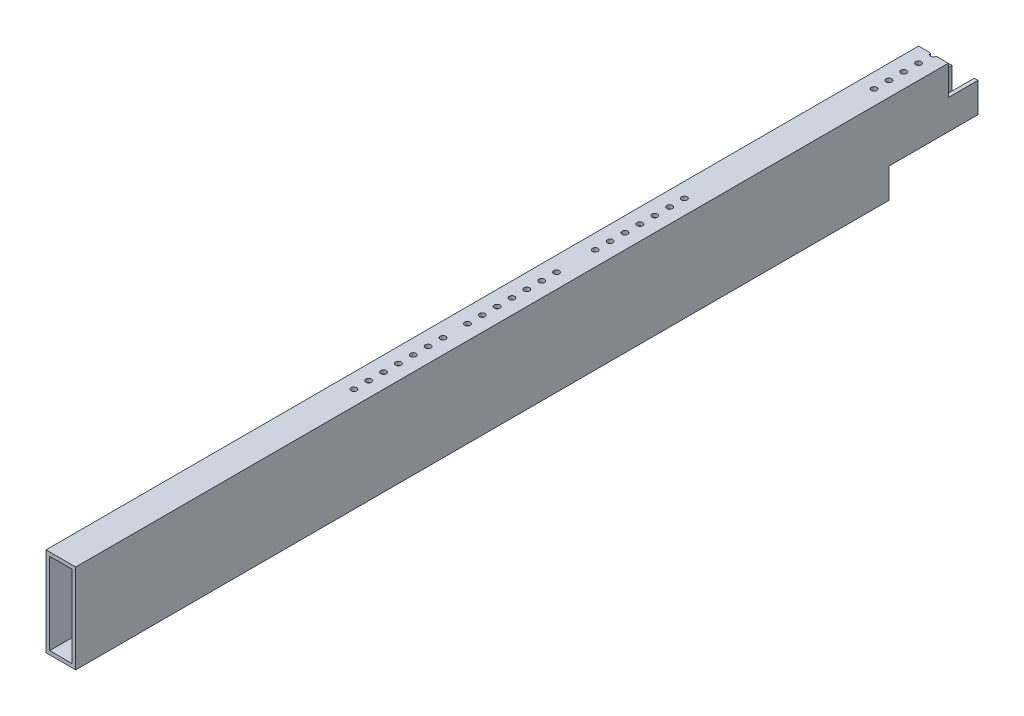
SolidWorks part; units mm, degrees
ref_plane "Front Plane" through (0, 0, 0) normal (0, 0, 1) x (1, 0, 0)
ref_plane "Top Plane" through (0, 0, 0) normal (0, 1, 0) x (1, 0, 0)
ref_plane "Right Plane" through (0, 0, 0) normal (1, 0, 0) x (0, 0, -1)
sketch "Sketch1" plane through (0, 0, 0) normal (0, 0, 1) x (1, 0, 0)
  line L1 (-12.7, -38.1) -> (12.7, -38.1)
  line L2 (-12.7, -38.1) -> (-12.7, 38.1)
  line L3 (-12.7, 38.1) -> (12.7, 38.1)
  line L4 (12.7, -38.1) -> (12.7, 38.1)
  line L5 (-12.7, -38.1) -> (12.7, 38.1) construction
  line L6 (-12.7, 38.1) -> (12.7, -38.1) construction
  point P0 (0, 0)
  dimension "D1" = 25.4
  dimension "D2" = 76.2
extrude "Boss-Extrude1" add sketch "Sketch1" along normal mid plane 771.398
shell "Shell1" thickness 3.175 removed face at (0, 0, -385.699) removed face at (0, 0, 385.699)
sketch "Sketch2" plane through (12.7, 0, 0) normal (1, 0, 0) x (0, 0, -1)
  line L1 (385.699, -38.1) -> (309.499, -38.1)
  line L2 (385.699, -38.1) -> (385.699, -12.7)
  line L3 (385.699, -12.7) -> (309.499, -12.7)
  line L4 (309.499, -38.1) -> (309.499, -12.7)
  dimension "D1" = 25.4
  dimension "D2" = 76.2
extrude "Cut-Extrude1" cut sketch "Sketch2" against normal through all
sketch "Sketch3" plane through (12.7, 0, 0) normal (1, 0, 0) x (0, 0, -1)
  line L1 (385.699, 38.1) -> (360.299, 38.1)
  line L2 (385.699, 38.1) -> (385.699, 12.7)
  line L3 (385.699, 12.7) -> (360.299, 12.7)
  line L4 (360.299, 38.1) -> (360.299, 12.7)
  dimension "D1" = 25.4
extrude "Cut-Extrude2" cut sketch "Sketch3" against normal through all
sketch "Sketch4" plane through (0, 38.1, 0) normal (0, 1, 0) x (1, 0, 0)
  line L0 (-12.7, 360.299) -> (12.7, 360.299) construction
  circle A0 centre (0, 147.3945) radius 2.3812
  circle A1 centre (0, 134.6945) radius 2.3812
  circle A2 centre (0, 121.9945) radius 2.3812
  circle A3 centre (0, 109.2945) radius 2.3812
  circle A4 centre (0, 96.5945) radius 2.3812
  circle A5 centre (0, 83.8945) radius 2.3812
  circle A6 centre (0, 71.1945) radius 2.3812
  circle A7 centre (0, 38.0987) radius 2.3812
  circle A8 centre (0, 25.3987) radius 2.3813
  circle A9 centre (0, 12.6987) radius 2.3813
  circle A10 centre (0, -0.0013) radius 2.3813
  circle A11 centre (0, -12.7013) radius 2.3812
  circle A12 centre (0, -25.4013) radius 2.3812
  circle A13 centre (0, -38.1013) radius 2.3812
  circle A15 centre (0, -58.9932) radius 2.3812
  circle A16 centre (0, -71.6932) radius 2.3812
  circle A17 centre (0, -84.3932) radius 2.3812
  circle A18 centre (0, -97.0932) radius 2.3812
  circle A19 centre (0, -109.7932) radius 2.3812
  circle A20 centre (0, -122.4932) radius 2.3812
  circle A21 centre (0, -135.1932) radius 2.3813
  point P33 (0, 360.299)
  dimension "D1" = 4.7625
  dimension "D3" = 12.7
  dimension "D4" = 12.7
  dimension "D5" = 12.7
  dimension "D6" = 12.7
  dimension "D7" = 12.7
  dimension "D8" = 12.7
  dimension "D9" = 322.2003
  dimension "D10" = 12.7
  dimension "D11" = 12.7
  dimension "D12" = 12.7
  dimension "D13" = 12.7
  dimension "D14" = 12.7
  dimension "D15" = 12.7
  dimension "D16" = 12.7
  dimension "D17" = 419.2922
  dimension "D18" = 12.7
  dimension "D19" = 12.7
  dimension "D20" = 12.7
  dimension "D21" = 12.7
  dimension "D22" = 12.7
  dimension "D2" = 212.9045
extrude "Cut-Extrude3" cut sketch "Sketch4" against normal up to next
sketch "Sketch5" plane through (0, 38.1, 0) normal (0, 1, 0) x (1, 0, 0)
  line L0 (-12.7, 360.299) -> (12.7, 360.299) construction
  circle A0 centre (0, 360.299) radius 2.3813
  circle A1 centre (0, 347.599) radius 2.3813
  circle A2 centre (0, 334.899) radius 2.3813
  circle A3 centre (0, 322.199) radius 2.3813
  circle A4 centre (0, 309.499) radius 2.3813
  dimension "D1" = 4.7625
  dimension "D3" = 12.7
  dimension "D4" = 12.7
  dimension "D5" = 12.7
  dimension "D8" = 0
  dimension "D2" = 12.7
extrude "Cut-Extrude4" cut sketch "Sketch5" against normal up to next
sketch "Sketch6" plane through (0, -38.1, 0) normal (0, -1, 0) x (1, 0, 0)
  line L0 (-12.7, -309.499) -> (12.7, -309.499) construction
  circle A0 centre (0, -309.499) radius 2.3813
  circle A1 centre (0, -296.799) radius 2.3813
  circle A2 centre (0, -284.099) radius 2.3813
  circle A3 centre (0, -258.699) radius 2.3813
  circle A6 centre (0, -271.399) radius 2.3813
  dimension "D1" = 4.7625
  dimension "D2" = 12.7
  dimension "D3" = 12.7
  dimension "D4" = 12.7
  dimension "D5" = 12.7
  dimension "D6" = 0
extrude "Cut-Extrude5" cut sketch "Sketch6" against normal up to next
